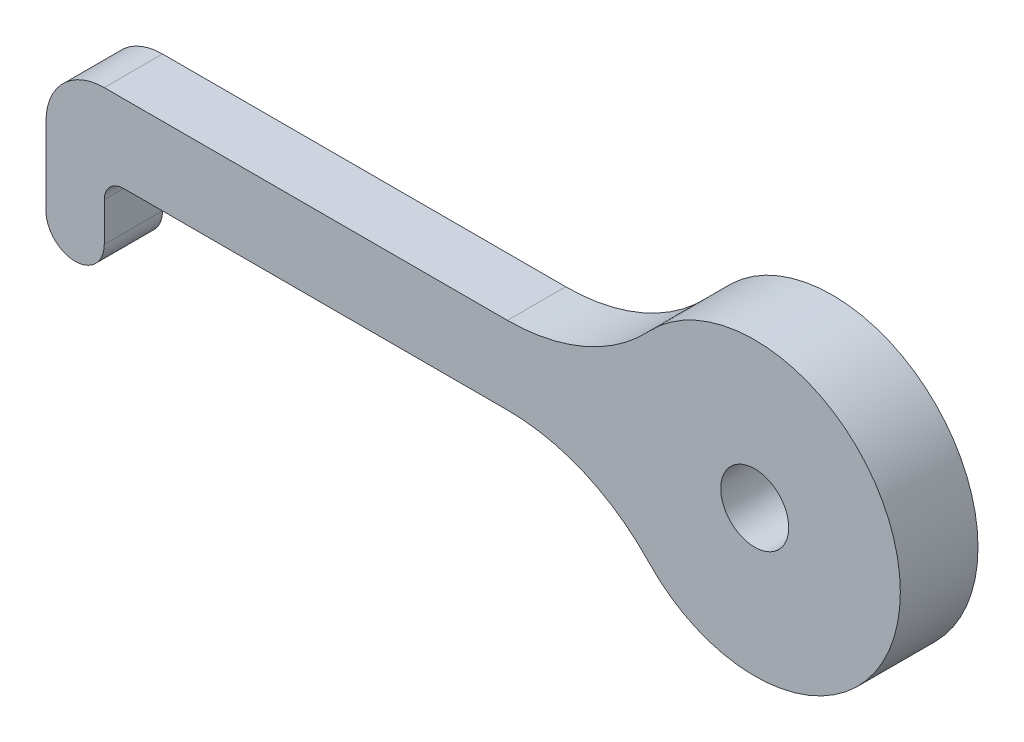
SolidWorks part; units mm, degrees
ref_plane "Plano frontal" through (0, 0, 0) normal (0, 0, 1) x (1, 0, 0)
ref_plane "Plano superior" through (0, 0, 0) normal (0, 1, 0) x (1, 0, 0)
ref_plane "Plano direito" through (0, 0, 0) normal (1, 0, 0) x (0, 0, -1)
sketch "Esboço1" plane through (0, 0, 0) normal (0, 0, 1) x (1, 0, 0)
  circle A0 centre (0, 0) radius 7.5
  circle A1 centre (0, 0) radius 1.75
  dimension "D1" = 3.5
  dimension "D2" = 15
extrude "Ressalto-extrusão1" add sketch "Esboço1" along normal blind 4
sketch "Esboço2" plane through (0, 0, 4) normal (0, 0, 1) x (1, 0, 0)
  line L0 (-7.2284, 2) -> (-36.5, 2)
  line L1 (-7.2284, -2) -> (-33.5, -2)
  line L2 (-36.5, -5) -> (-36.5, 2)
  line L5 (-33.5, -5) -> (-33.5, -2)
  arc A0 (-7.2284, 2) -> (-7.2284, -2) centre (0, 0) ccw
  arc A1 (-36.5, -5) -> (-33.5, -5) centre (-35, -5) ccw
  circle A2 centre (0, 0) radius 1.75 construction
  dimension "D2" = 35
  dimension "D5" = 5
  dimension "D6" = 7.5
  dimension "D1" = 3
  dimension "D3" = 2
  dimension "D4" = 2
extrude "Ressalto-extrusão2" add sketch "Esboço2" against normal blind 3
fillet "Filete1" radius 3 1 edges at (-36.5, 2, 2.5)
fillet "Filete2" radius 1 1 edges at (-33.5, -2, 2.5)
fillet "Filete3" radius 10 2 edges at (-7.2284, -2, 2.5) (-7.2284, 2, 2.5)
